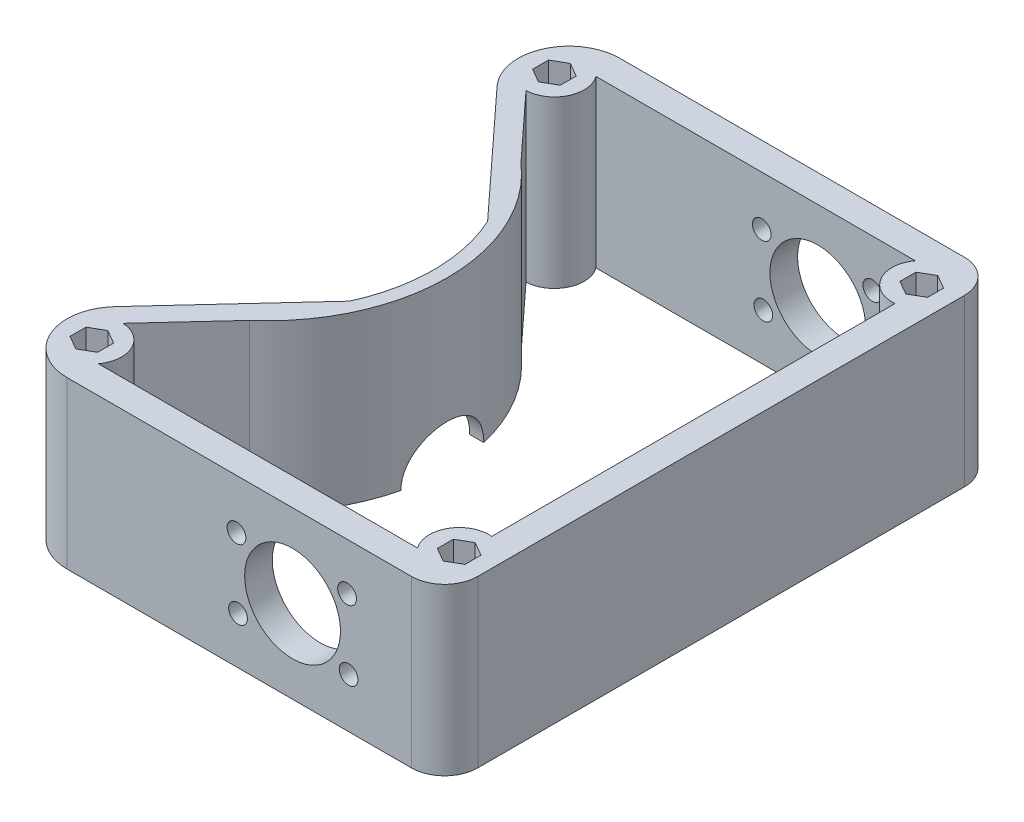
SolidWorks part; units mm, degrees
material "TPU"
ref_plane "Front Plane" through (0, 0, 0) normal (0, 0, 1) x (1, 0, 0)
ref_plane "Top Plane" through (0, 0, 0) normal (0, 1, 0) x (1, 0, 0)
ref_plane "Right Plane" through (0, 0, 0) normal (1, 0, 0) x (0, 0, -1)
sketch "Sketch1" plane through (0, 0, 0) normal (0, 1, 0) x (1, 0, 0)
  line L0 (66.675, 17.145) -> (66.675, 128.905) construction
  line L1 (-28.575, 9.525) -> (66.675, 9.525)
  line L2 (-28.575, 9.525) -> (-28.575, 15.875)
  line L3 (-28.575, 15.875) -> (66.675, 15.875)
  line L4 (66.675, 9.525) -> (66.675, 15.875)
  line L5 (-28.575, 9.525) -> (66.675, 15.875) construction
  line L6 (-28.575, 15.875) -> (66.675, 9.525) construction
  line L9 (-28.575, 9.525) -> (59.055, 9.525) construction
  point P0 (19.05, 12.7)
  point P15 (19.05, 9.525)
  dimension "D1" = 95.25
  dimension "D2" = 6.35
extrude "Boss-Extrude1" add sketch "Sketch1" along normal blind 38.1
sketch "Sketch2" plane through (0, 38.1, 0) normal (0, 1, 0) x (1, 0, 0)
  line L1 (60.325, 9.525) -> (66.675, 9.525)
  line L2 (60.325, 9.525) -> (60.325, 136.525)
  line L3 (60.325, 136.525) -> (66.675, 136.525)
  line L4 (66.675, 9.525) -> (66.675, 136.525)
  line L6 (32.8756, 15.875) -> (32.8756, 130.175) construction
  line L7 (-20.4, 15.875) -> (58.5, 15.875) construction
  line L8 (58.5, 130.175) -> (-20.4, 130.175) construction
  dimension "D1" = 127
  dimension "D2" = 6.35
extrude "Boss-Extrude2" add sketch "Sketch2" against normal up to surface (38.1 mm away) up to face at (19.05, 0, -12.7)
sketch "Sketch3" plane through (0, 38.1, 0) normal (0, 1, 0) x (1, 0, 0)
  line L0 (-28.575, 15.875) -> (-28.575, 9.525) construction
  line L1 (60.325, 136.525) -> (-28.575, 136.525)
  line L2 (60.325, 136.525) -> (60.325, 130.175)
  line L3 (60.325, 130.175) -> (-28.575, 130.175)
  line L4 (-28.575, 136.525) -> (-28.575, 130.175)
extrude "Boss-Extrude3" add sketch "Sketch3" against normal up to surface (38.1 mm away) up to face at (32.8083, 0, -53.975)
sketch "Sketch4" plane through (0, 0, -136.525) normal (0, 0, -1) x (-1, 0, 0)
  line L0 (3.175, 38.1) -> (-66.675, 38.1) construction
  line L1 (-66.675, 19.05) -> (3.175, 19.05) construction
  line L2 (-66.675, 0) -> (-66.675, 38.1) construction
  line L5 (28.575, 19.05) -> (3.175, 19.05) construction
  line L6 (28.575, 0) -> (28.575, 38.1) construction
  circle A0 centre (-31.75, 19.05) radius 11
  point P7 (-31.75, 38.1)
  dimension "D1" = 22
  dimension "D2" = 25.4
extrude "Cut-Extrude1" cut sketch "Sketch4" against normal through all contours A0 region at (31.75, 19.05, -136.525)
sketch "Sketch5" plane through (0, 0, -136.525) normal (0, 0, -1) x (-1, 0, 0)
  circle A0 centre (-18.8777, 26.7049) radius 2.1527
  circle A1 centre (-19.2285, 10.8337) radius 2.1527
  circle A2 centre (-44.6223, 11.3951) radius 2.1527
  circle A3 centre (-44.2715, 27.2663) radius 2.1526
  circle A4 centre (-44.6223, 11.3951) radius 2.1527 construction
  circle A5 centre (-18.8777, 26.7049) radius 2.1526 construction
  circle A6 centre (-19.2285, 10.8337) radius 2.1527 construction
  circle A9 centre (-44.2715, 27.2663) radius 2.1526 construction
extrude "Cut-Extrude2" cut sketch "Sketch5" against normal through all
fillet "Fillet1" radius 7.62 2 edges at (66.675, 19.05, -9.525) (66.675, 19.05, -136.525)
sketch "Sketch10" plane through (0, 38.1, 0) normal (0, 1, 0) x (1, 0, 0)
  line L0 (-28.575, 9.525) -> (59.055, 9.525) construction
  line L2 (-28.575, 15.875) -> (-28.575, 9.525)
  line L5 (66.675, 73.025) -> (-141.5874, 73.025) construction
  line L7 (-28.575, 136.525) -> (-31.75, 136.525)
  line L11 (-31.75, 25.781) -> (-2.821, 57.15)
  line L15 (-28.575, 15.875) -> (-28.575, 22.225)
  line L16 (-28.575, 22.225) -> (-10.4944, 41.8306)
  line L17 (-28.575, 123.825) -> (-10.4944, 104.2194)
  line L18 (-31.75, 120.269) -> (-2.821, 88.9)
  line L19 (-10.4944, 41.8306) -> (-2.821, 57.15) construction
  line L22 (-28.575, 136.525) -> (-28.575, 123.825)
  line L26 (-31.75, 136.525) -> (-31.75, 120.269)
  line L27 (-31.75, 25.781) -> (-31.75, 9.525)
  line L28 (-31.75, 9.525) -> (-28.575, 9.525)
  line L29 (66.675, 17.145) -> (66.675, 128.905) construction
  arc A0 (-2.821, 57.15) -> (-2.821, 88.9) centre (-37.4562, 73.025) ccw
  arc A2 (-10.4944, 104.2194) -> (-10.4944, 41.8306) centre (-37.4562, 73.025) cw
  dimension "D7" = 31.75
  dimension "D6" = 38.1
  dimension "D1" = 16.256
  dimension "D2" = 3.175
  dimension "D3" = 12.7
  dimension "D4" = 42.672
  dimension "D5" = 26.67
extrude "Boss-Extrude4" add sketch "Sketch10" against normal up to surface (38.1 mm away) up to face at (26.0966, 0, -73.025)
sketch "Sketch12" plane through (60.325, 0, 0) normal (-1, 0, 0) x (0, 0, 1)
  line L0 (-88.9, 0) -> (-82.55, 0) construction
  line L1 (-88.9, 0) -> (-57.15, 0) construction
  line L2 (-57.15, 0) -> (-63.5, 0) construction
  line L3 (-82.55, 0) -> (-63.5, 0)
  arc A0 (-82.55, 0) -> (-63.5, 0) centre (-73.025, 0) cw
  dimension "D1" = 19.05
extrude "Cut-Extrude8" cut sketch "Sketch12" along normal up to surface (92.075 mm away) up to face at (-31.75, 19.05, -128.397)
fillet "Fillet2" 2 edges at (-31.75, 19.05, -120.269) (-31.75, 19.05, -136.525) type full round first side face at (-17.2855, 19.05, -104.5845) second side face at (42.1188, 27.2663, -136.525) middle face at (-31.75, 19.05, -128.397)
fillet "Fillet3" 2 edges at (-31.75, 19.05, -25.781) (-31.75, 19.05, -9.525) type full round first side face at (-17.2855, 19.05, -41.4655) second side face at (42.1188, 27.2663, -9.525) middle face at (-31.75, 19.05, -17.653)
fillet "Fillet4" radius 6.35 2 edges at (60.325, 19.05, -130.175) (60.325, 19.05, -15.875)
sketch "Sketch15" plane through (0, 38.1, 0) normal (0, 1, 0) x (1, 0, 0)
  line L0 (0.6438, 73.025) -> (66.675, 73.025) construction
  line L1 (66.675, 17.145) -> (66.675, 128.905) construction
  line L2 (-24.7273, 23.5658) -> (-24.7273, 26.7408) construction
  line L3 (-21.5523, 21.7327) -> (-24.7273, 23.5658)
  line L4 (-24.7273, 23.5658) -> (-27.9023, 21.7327)
  line L5 (-27.9023, 21.7327) -> (-27.9023, 18.0665)
  line L6 (-27.9023, 18.0665) -> (-24.7273, 16.2334)
  line L7 (-24.7273, 16.2334) -> (-21.5523, 18.0665)
  line L8 (-21.5523, 18.0665) -> (-21.5523, 21.7327)
  line L9 (-30.7676, 16.5233) -> (63.5, 69.215) construction
  line L10 (63.5, 69.215) -> (63.5, 9.525) construction
  line L11 (59.6523, 129.8166) -> (56.4773, 127.9835)
  line L12 (59.055, 9.525) -> (63.5, 9.525) construction
  line L13 (60.325, 69.215) -> (66.675, 69.215) construction
  line L14 (60.325, 123.825) -> (60.325, 22.225) construction
  line L15 (-21.5523, 127.9835) -> (-21.5523, 124.3173)
  line L16 (-24.7273, 129.8166) -> (-21.5523, 127.9835)
  line L17 (-27.9023, 127.9835) -> (-24.7273, 129.8166)
  line L18 (-27.9023, 124.3173) -> (-27.9023, 127.9835)
  line L19 (-24.7273, 122.4842) -> (-27.9023, 124.3173)
  line L20 (-21.5523, 124.3173) -> (-24.7273, 122.4842)
  line L21 (17.4625, 120.6024) -> (17.4625, 25.4476) construction
  line L22 (62.8273, 127.9835) -> (59.6523, 129.8166)
  line L23 (62.8273, 124.3173) -> (62.8273, 127.9835)
  line L24 (-31.75, 124.8361) -> (-31.75, 21.2139) construction
  line L25 (-31.75, 73.025) -> (66.675, 73.025) construction
  line L26 (59.6523, 122.4842) -> (62.8273, 124.3173)
  line L27 (56.4773, 124.3173) -> (59.6523, 122.4842)
  line L28 (56.4773, 127.9835) -> (56.4773, 124.3173)
  line L29 (56.4773, 18.0665) -> (56.4773, 21.7327)
  line L30 (59.6523, 16.2334) -> (56.4773, 18.0665)
  line L31 (62.8273, 18.0665) -> (59.6523, 16.2334)
  line L32 (62.8273, 21.7327) -> (62.8273, 18.0665)
  line L33 (59.6523, 23.5658) -> (62.8273, 21.7327)
  line L34 (56.4773, 21.7327) -> (59.6523, 23.5658)
  arc A2 (-26.3148, 17.15) -> (-23.1398, 17.15) centre (-24.7273, 19.8996) ccw construction
  circle A3 centre (59.6523, 126.1504) radius 6.8412
  arc A4 (-2.821, 57.15) -> (-2.821, 88.9) centre (-37.4562, 73.025) ccw construction
  circle A7 centre (-24.7273, 19.8996) radius 6.8412
  arc A8 (-28.6538, 29.1383) -> (-20.0611, 9.525) centre (-20.0611, 21.2139) ccw construction
  circle A9 centre (-24.7273, 19.8996) radius 3.175 construction
  circle A10 centre (-24.7273, 126.1504) radius 6.8412
  arc A11 (-20.0611, 136.525) -> (-28.6538, 116.9117) centre (-20.0611, 124.8361) ccw construction
  circle A12 centre (59.6523, 19.8996) radius 6.8412
  point P49 (17.4625, 73.025)
  line M11 (60.325, 123.825) -> (60.325, 22.225)
  arc M12 (60.325, 22.225) -> (53.975, 15.875) centre (53.975, 22.225) cw
  line M13 (53.975, 15.875) -> (-28.575, 15.875)
  line M15 (-28.575, 22.225) -> (-10.4944, 41.8306)
  line M17 (-10.4944, 104.2194) -> (-28.575, 123.825)
  line M19 (-28.575, 130.175) -> (53.975, 130.175)
  arc M20 (53.975, 130.175) -> (60.325, 123.825) centre (53.975, 123.825) cw
  dimension "D1" = 3.175
  dimension "D2" = 3.81
extrude "Boss-Extrude7" add sketch "Sketch15" against normal up to surface (38.1 mm away) contours A7 L8 L7 L6 L5 L4 L3 M15 M13 | A7 L3 L8 M13 M15 | A12 L29 L34 L33 M13 M12 M11 | A12 L33 L32 L31 L30 L29 M11 M12 M13 | A3 L28 L11 L22 L23 L26 M11 M19 M20 | A3 L26 L27 L28 M19 M11 M20 | A10 L20 L19 L18 L17 L16 L15 M17 M19 | A10 L15 L20 M19 M17 region at (58.6883, 38.1, -129.4728) region at (56.0673, 38.1, -124.3501) region at (-30.7182, 38.1, -17.0187) region at (64.5854, 38.1, -24.3693) region at (56.0673, 38.1, -21.6999) region at (-18.4056, 38.1, -128.2066) up to face at (10.1062, 0, -73.025)
sketch "Sketch21" plane through (0, 38.1, 0) normal (0, 1, 0) x (1, 0, 0)
  line L0 (60.325, 119.3424) -> (60.325, 26.7076) construction
  line L1 (-21.5523, 21.7327) -> (-24.7273, 23.5658)
  line L2 (-24.7273, 23.5658) -> (-27.9023, 21.7327)
  line L3 (-27.9023, 21.7327) -> (-27.9023, 18.0665)
  line L4 (-27.9023, 18.0665) -> (-24.7273, 16.2334)
  line L5 (-24.7273, 16.2334) -> (-21.5523, 18.0665)
  line L6 (-21.5523, 18.0665) -> (-21.5523, 21.7327)
  line L7 (3.7752, 73.025) -> (60.325, 73.025) construction
  line L9 (17.4625, 120.6024) -> (17.4625, 25.4476) construction
  line L10 (56.4773, 18.0665) -> (56.4773, 21.7327)
  line L11 (59.6523, 16.2334) -> (56.4773, 18.0665)
  line L12 (62.8273, 18.0665) -> (59.6523, 16.2334)
  line L13 (62.8273, 21.7327) -> (62.8273, 18.0665)
  line L14 (59.6523, 23.5658) -> (62.8273, 21.7327)
  line L15 (56.4773, 21.7327) -> (59.6523, 23.5658)
  line L16 (59.6523, 129.8166) -> (56.4773, 127.9835)
  line L17 (62.8273, 127.9835) -> (59.6523, 129.8166)
  line L18 (62.8273, 124.3173) -> (62.8273, 127.9835)
  line L19 (59.6523, 122.4842) -> (62.8273, 124.3173)
  line L20 (56.4773, 124.3173) -> (59.6523, 122.4842)
  line L21 (56.4773, 127.9835) -> (56.4773, 124.3173)
  line L22 (-21.5523, 127.9835) -> (-21.5523, 124.3173)
  line L23 (-24.7273, 129.8166) -> (-21.5523, 127.9835)
  line L24 (-27.9023, 127.9835) -> (-24.7273, 129.8166)
  line L25 (-27.9023, 124.3173) -> (-27.9023, 127.9835)
  line L26 (-24.7273, 122.4842) -> (-27.9023, 124.3173)
  line L27 (-21.5523, 124.3173) -> (-24.7273, 122.4842)
  circle A0 centre (-24.7273, 19.8996) radius 3.175 construction
  arc A1 (-10.4944, 41.8306) -> (-10.4944, 104.2194) centre (-37.4562, 73.025) ccw construction
extrude "Cut-Extrude12" cut sketch "Sketch21" against normal through all
